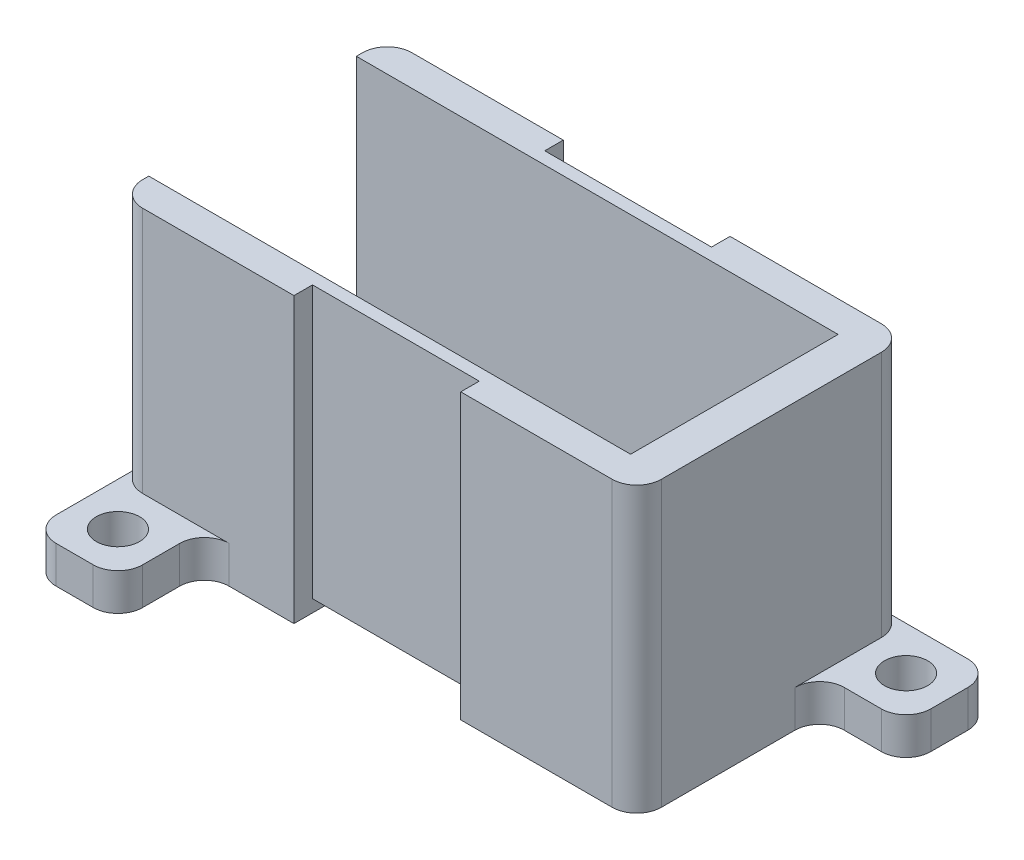
SolidWorks part; units mm, degrees
ref_plane "Front Plane" through (0, 0, 0) normal (0, 0, 1) x (1, 0, 0)
ref_plane "Top Plane" through (0, 0, 0) normal (0, 1, 0) x (1, 0, 0)
ref_plane "Right Plane" through (0, 0, 0) normal (1, 0, 0) x (0, 0, -1)
sketch "Sketch1" plane through (0, 0, 0) normal (0, 1, 0) x (1, 0, 0)
  line L0 (-33, 8.6) -> (30, 8.6)
  line L1 (-33, -30.4) -> (33, -30.4)
  line L2 (-33, -30.4) -> (-33, 11.1)
  line L4 (33, -30.4) -> (33, 30.4)
  line L5 (-33, 11.1) -> (30, 11.1)
  line L6 (30, 11.1) -> (30, 27.9)
  line L7 (30, 8.6) -> (30, -27.9)
  line L8 (30, -27.9) -> (-33, -27.9)
  line L9 (30, 27.9) -> (-9, 27.9)
  line L10 (-19, -28.9) -> (-5.5, -28.9)
  line L11 (-19, -28.9) -> (-19, -30.4)
  line L12 (-19, -30.4) -> (-5.5, -30.4)
  line L13 (-5.5, -28.9) -> (-5.5, -30.4)
  line L14 (-19, -28.9) -> (-5.5, -30.4) construction
  line L15 (-19, -30.4) -> (-5.5, -28.9) construction
  line L16 (-19, 9.6) -> (-5.5, 9.6)
  line L17 (-19, 9.6) -> (-19, 11.1)
  line L18 (-19, 11.1) -> (-5.5, 11.1)
  line L19 (-5.5, 9.6) -> (-5.5, 11.1)
  line L20 (-19, 9.6) -> (-5.5, 11.1) construction
  line L21 (-19, 11.1) -> (-5.5, 9.6) construction
  line L22 (-9, 27.9) -> (-9, 30.4)
  line L23 (-9, 30.4) -> (33, 30.4)
  line L24 (-9, 27.9) -> (-9, 11.1)
  line L25 (5.25, 28.9) -> (18.75, 28.9)
  line L26 (5.25, 28.9) -> (5.25, 30.4)
  line L27 (5.25, 30.4) -> (18.75, 30.4)
  line L28 (18.75, 28.9) -> (18.75, 30.4)
  line L29 (5.25, 28.9) -> (18.75, 30.4) construction
  line L30 (5.25, 30.4) -> (18.75, 28.9) construction
  line L31 (5.25, 10.1) -> (18.75, 10.1)
  line L32 (5.25, 10.1) -> (5.25, 8.6)
  line L33 (5.25, 8.6) -> (18.75, 8.6)
  line L34 (18.75, 10.1) -> (18.75, 8.6)
  line L35 (5.25, 10.1) -> (18.75, 8.6) construction
  line L36 (5.25, 8.6) -> (18.75, 10.1) construction
  line L37 (5.25, 28.9) -> (5.25, 10.1)
  line L38 (18.75, 10.1) -> (18.75, 28.9)
  line L39 (-19, 9.6) -> (-19, -28.9)
  line L40 (-5.5, -28.9) -> (-5.5, 9.6)
  line L41 (30, 11.1) -> (33, 11.1)
  line L42 (-26, -37.4) -> (-33, -37.4)
  line L43 (-26, -37.4) -> (-26, -30.4)
  line L44 (-26, -30.4) -> (-33, -30.4)
  line L45 (-33, -37.4) -> (-33, -30.4)
  line L46 (-26, -37.4) -> (-33, -30.4) construction
  line L47 (-26, -30.4) -> (-33, -37.4) construction
  line L48 (26, -37.4) -> (33, -37.4)
  line L49 (26, -37.4) -> (26, -30.4)
  line L50 (26, -30.4) -> (33, -30.4)
  line L51 (33, -37.4) -> (33, -30.4)
  line L52 (26, -37.4) -> (33, -30.4) construction
  line L53 (26, -30.4) -> (33, -37.4) construction
  line L54 (-2, 37.4) -> (-9, 37.4)
  line L55 (-2, 37.4) -> (-2, 30.4)
  line L56 (-2, 30.4) -> (-9, 30.4)
  line L57 (-9, 37.4) -> (-9, 30.4)
  line L58 (-2, 37.4) -> (-9, 30.4) construction
  line L59 (-2, 30.4) -> (-9, 37.4) construction
  line L60 (-9, 11.1) -> (-9, 8.6)
  line L61 (30, 8.6) -> (33, 8.6)
  circle A0 centre (-29.5, -33.9) radius 1.75
  circle A1 centre (29.5, -33.9) radius 1.75
  circle A2 centre (-5.5, 33.9) radius 1.75
  point P0 (12, 29.65)
  point P8 (-12.25, -29.65)
  point P15 (-12.25, 10.35)
  point P27 (12, 9.35)
  point P32 (-29.5, -33.9)
  point P34 (29.5, -33.9)
  point P37 (0, -30.4)
  point P39 (33, 0)
  point P41 (12, 30.4)
  point P42 (-5.5, 33.9)
  dimension "D12" = 3.5
  dimension "D1" = 36.5
  dimension "D2" = 63
  dimension "D3" = 2.5
  dimension "D4" = 3
  dimension "D5" = 2.5
  dimension "D6" = 2.5
  dimension "D7" = 13.5
  dimension "D8" = 1.5
  dimension "D9" = 14
  dimension "D10" = 16.8
  dimension "D11" = 39
  dimension "D13" = 7
extrude "Boss-Extrude1" add sketch "Sketch1" along normal blind 3 contours L37 L9 L24 L18 L5 | L37 L26 L23 L22 L9 | L40 L0 L32 L37 L5 L19 | L16 L60 L0 L40 | L18 L60 L16 L19 | L31 L38 L5 L37 | L34 L31 L32 L0 | L0 L61 L4 L41 L5 L38 L34 | L6 L41 L4 L23 L28 L38 L9 | L9 L38 L25 L37 | L25 L28 L23 L26 | L38 L5 L6 L9 | L5 L38 L9 L37 region at (12, 0, -9.35) region at (-0.125, 0, -9.85) region at (25.875, 0, -9.85) region at (-7.25, 0, -9.1) region at (12, 0, -10.6) region at (-7.25, 0, -10.35) region at (12, 0, -19.5) region at (-1.875, 0, -19.5) region at (24.375, 0, -19.5) region at (12, 0, -28.4) region at (-1.875, 0, -29.15) region at (31.5, 0, -11.3399) region at (12, 0, -29.65)
extrude "Boss-Extrude2" add sketch "Sketch1<5>" along normal blind 20 from surface contours L37 L26 L23 L22 L9 | L40 L0 L32 L37 L5 L19 | L16 L60 L0 L40 | L18 L60 L16 L19 | L0 L61 L4 L41 L5 L38 L34 | L31 L38 L5 L37 | L6 L41 L4 L23 L28 L38 L9 | L9 L38 L25 L37 region at (-0.125, 0, -9.85) region at (25.875, 0, -9.85) region at (-7.25, 0, -9.1) region at (12, 0, -10.6) region at (-7.25, 0, -10.35) region at (12, 0, -28.4) region at (-1.875, 0, -29.15) region at (31.5, 0, -11.3399) starting at face at (12, 3, -19.5)
sketch "Sketch1<5>" plane through (0, 0, 0) normal (0, 1, 0) x (1, 0, 0) same geometry as "Sketch1"
extrude "Cut-Extrude1" cut sketch "Sketch1<7>" against normal through all both and the other way through all contours L25 L28 L23 L26 | L34 L31 L32 L0 region at (12, 0, -9.35) region at (12, 0, -29.65)
sketch "Sketch1<7>" plane through (0, 0, 0) normal (0, 1, 0) x (1, 0, 0) same geometry as "Sketch1"
extrude "Cut-Extrude2" cut sketch "Sketch1<8>" along normal blind 1 contours L5 L38 L9 L37 | L25 L28 L23 L26 | L9 L38 L25 L37 | L34 L31 L32 L0 | L31 L38 L5 L37 region at (12, 0, -9.35) region at (12, 0, -10.6) region at (12, 0, -19.5) region at (12, 0, -28.4) region at (12, 0, -29.65)
sketch "Sketch1<8>" plane through (0, 0, 0) normal (0, 1, 0) x (1, 0, 0) same geometry as "Sketch1"
sketch "Sketch2" plane through (0, 0, 0) normal (0, 1, 0) x (-1, 0, 0)
  line L14 (2, -1.6) -> (9, -1.6)
  line L15 (2, -1.6) -> (2, -8.6)
  line L20 (2, -8.6) -> (9, -8.6)
  line L21 (9, -1.6) -> (9, -8.6)
  line L22 (2, -1.6) -> (9, -8.6) construction
  line L23 (2, -8.6) -> (9, -1.6) construction
  line L24 (-40, -23.4) -> (-33, -23.4)
  line L25 (-40, -23.4) -> (-40, -30.4)
  line L26 (-40, -30.4) -> (-33, -30.4)
  line L27 (-33, -23.4) -> (-33, -30.4)
  line L28 (-40, -23.4) -> (-33, -30.4) construction
  line L29 (-40, -30.4) -> (-33, -23.4) construction
  circle A4 centre (-36.5, -26.9) radius 1.75
  circle A5 centre (5.5, -5.1) radius 1.75
  point P0 (5.5, -5.1)
  point P5 (-36.5, -26.9)
  dimension "D1" = 7
  dimension "D2" = 3.5
extrude "Boss-Extrude3" add sketch "Sketch2" along normal up to surface (3 mm away) contours L21 L14 L15 | L24 L27 L26 L25 A5 | L14 L21 L20 L15 A4 region at (-5.5, 0, -1.699) region at (36.5, 0, -23.499) up to face at (10.5, 3, -19.5)
fillet "Fillet1" radius 2 10 edges at (-9, 11.5, -30.4) (-9, 13, -8.6) (-9, 1.5, -1.6) (-2, 1.5, -1.6) (-2, 1.5, -8.6) (33, 11.5, -8.6) (33, 13, -30.4) (40, 1.5, -23.4) (33, 1.5, -23.4) (40, 1.5, -30.4)
